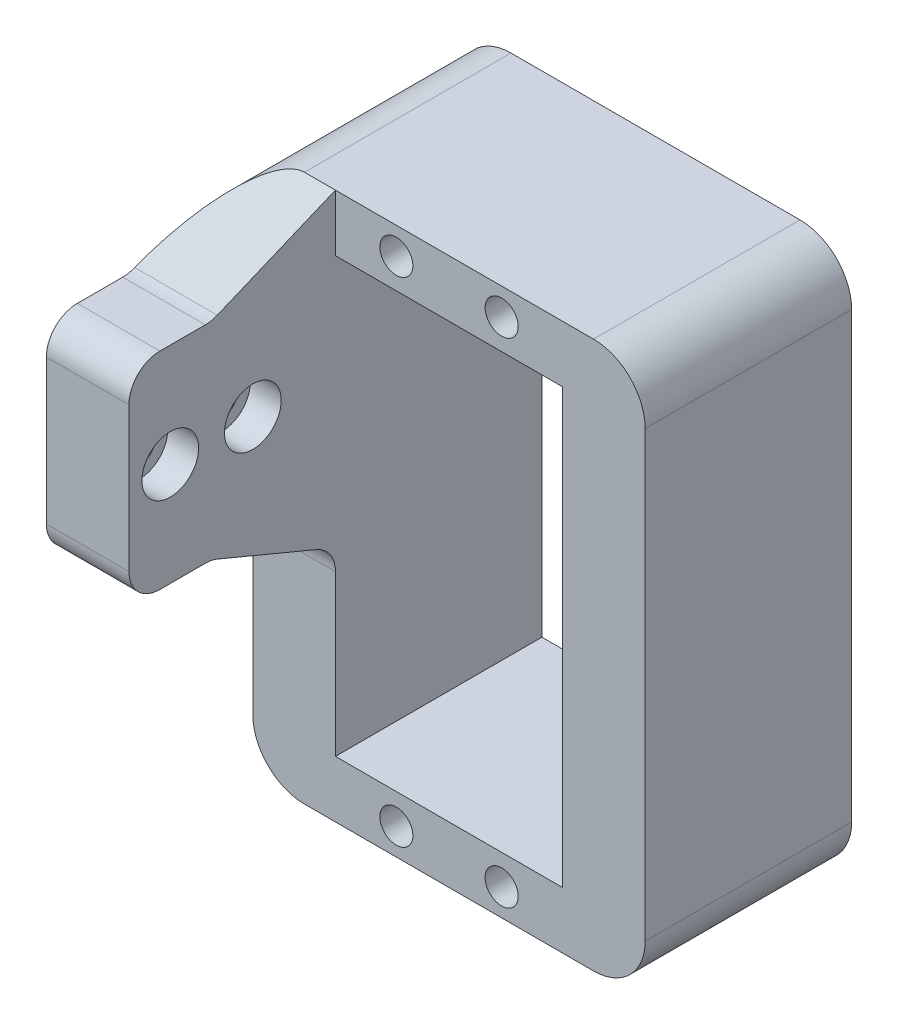
SolidWorks part; units mm, degrees
ref_plane "Front Plane" through (0, 0, 0) normal (0, 0, 1) x (1, 0, 0)
ref_plane "Top Plane" through (0, 0, 0) normal (0, 1, 0) x (1, 0, 0)
ref_plane "Right Plane" through (0, 0, 0) normal (1, 0, 0) x (0, 0, -1)
sketch "Sketch1" plane through (0, 0, 0) normal (0, 0, 1) x (1, 0, 0)
  line L1 (-11, 21) -> (11, 21)
  line L2 (-11, 21) -> (-11, -21)
  line L3 (-11, -21) -> (11, -21)
  line L4 (11, 21) -> (11, -21)
  line L5 (-11, 21) -> (11, -21) construction
  line L6 (-11, -21) -> (11, 21) construction
  line L8 (-19, 26.5) -> (19, 26.5)
  line L9 (-19, 26.5) -> (-19, -26.5)
  line L10 (-19, -26.5) -> (19, -26.5)
  line L11 (19, 26.5) -> (19, -26.5)
  line L12 (-19, 26.5) -> (19, -26.5) construction
  line L13 (-19, -26.5) -> (19, 26.5) construction
  point P0 (0, 0)
  point P6 (0, 0)
  dimension "D1" = 22
  dimension "D2" = 42
  dimension "D4" = 8
  dimension "D3" = 53
extrude "Boss-Extrude1" add sketch "Sketch1" along normal blind 20
sketch "Sketch2" plane through (0, 0, 20) normal (0, 0, 1) x (1, 0, 0)
  line L0 (-19, 26.5) -> (-19, -26.5) construction
  line L1 (-19, 1.5) -> (-11, 1.5)
  line L2 (-19, 1.5) -> (-19, 21.5)
  line L3 (-19, 21.5) -> (-11, 21.5)
  line L4 (-11, 1.5) -> (-11, 21.5)
  line L5 (-11, 21) -> (-11, -21) construction
  line L7 (19, 26.5) -> (-19, 26.5) construction
  dimension "D1" = 20
  dimension "D2" = 5
extrude "Boss-Extrude2" add sketch "Sketch2" along normal blind 20
sketch "Sketch3" plane through (-11, 0, 0) normal (1, 0, 0) x (0, 0, -1)
  line L0 (-40, 1.5) -> (-40, 21.5) construction
  line L1 (-20, -26.5) -> (-20, 26.5) construction
  circle A0 centre (-36, 11.5) radius 2.75
  circle A1 centre (-28, 11.5) radius 2.75
  circle A2 centre (-36, 11.5) radius 1.6
  circle A3 centre (-28, 11.5) radius 1.6
  point P9 (-40, 11.5)
  dimension "D1" = 5.5
  dimension "D4" = 3.2
  dimension "D2" = 4
  dimension "D3" = 8
extrude "Cut-Extrude1" cut sketch "Sketch3" against normal blind 3
extrude "Cut-Extrude2" cut sketch "Sketch3<2>" against normal through all contours A2 | A3 region at (-11, 11.5, 36) region at (-11, 11.5, 28)
sketch "Sketch3<2>" plane through (-11, 0, 0) normal (1, 0, 0) x (0, 0, -1) same geometry as "Sketch3"
sketch "Sketch4" plane through (0, 0, 0) normal (0, 0, -1) x (-1, 0, 0)
  circle A0 centre (-5.1, -23.9) radius 1.6
  circle A1 centre (5.1, -23.9) radius 1.6
  circle A2 centre (-5.1, 23.9) radius 1.6
  circle A3 centre (5.1, 23.9) radius 1.6
  dimension "D1" = 3.2
extrude "Cut-Extrude3" cut sketch "Sketch4" against normal through all
sketch "Sketch5" plane through (-19, 0, 0) normal (-1, 0, 0) x (0, 0, 1)
  line L0 (32, 1.5) -> (20, -3.5)
  line L1 (40, 1.5) -> (20, 1.5) construction
  line L2 (20, 1.5) -> (20, -26.5) construction
  line L3 (20, -3.5) -> (20, 1.5)
  line L4 (20, 1.5) -> (32, 1.5)
  line L5 (20, 26.5) -> (20, 21.5)
  line L6 (20, 21.5) -> (32, 21.5)
  line L7 (40, 21.5) -> (20, 21.5) construction
  line L8 (32, 21.5) -> (20, 26.5)
  dimension "D1" = 12
extrude "Boss-Extrude3" add sketch "Sketch5" against normal up to surface (8 mm away) up to face at (-11, 11.5, 33.25)
fillet "Fillet2" radius 3 5 edges at (-15, 21.5, 32) (-15, 21.5, 40) (-15, -3.5, 20) (-15, 1.5, 40) (-15, 1.5, 32)
fillet "Fillet1" radius 5 4 edges at (-19, -26.5, 10) (19, -26.5, 10) (-19, 26.5, 10) (19, 26.5, 10)
